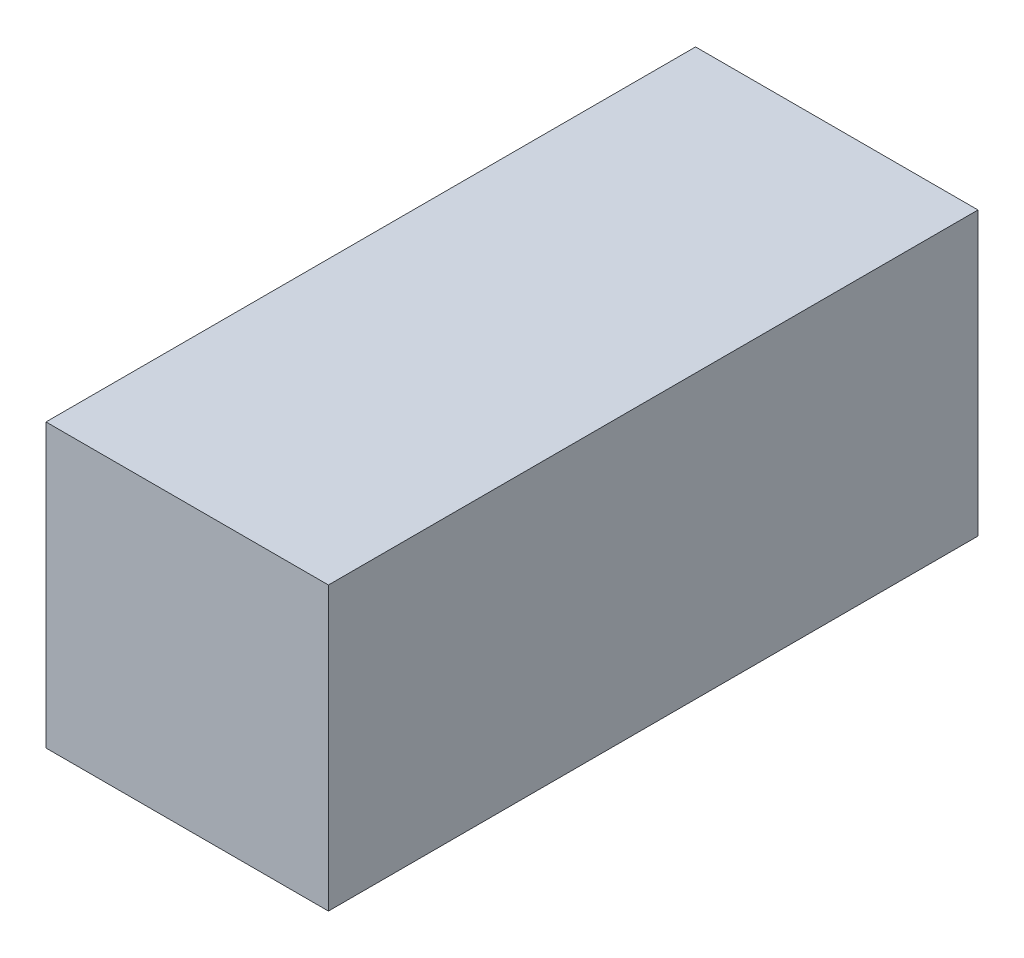
SolidWorks part; units mm, degrees
ref_plane "Front Plane" through (0, 0, 0) normal (0, 0, 1) x (1, 0, 0)
ref_plane "Top Plane" through (0, 0, 0) normal (0, 1, 0) x (1, 0, 0)
ref_plane "Right Plane" through (0, 0, 0) normal (1, 0, 0) x (0, 0, -1)
sketch "Sketch1" plane through (0, 0, 0) normal (0, 0, 1) x (1, 0, 0)
  line L1 (-50, -50) -> (50, -50)
  line L2 (-50, -50) -> (-50, 50)
  line L3 (-50, 50) -> (50, 50)
  line L4 (50, -50) -> (50, 50)
  line L5 (-50, -50) -> (50, 50) construction
  line L6 (-50, 50) -> (50, -50) construction
  point P0 (0, 0)
  dimension "D1" = 100
extrude "Boss-Extrude1" add sketch "Sketch1" along normal blind 230
ref_plane "Plane1" through (0, 0, 0) normal (-0.7071, 0.7071, 0) x (0.7071, 0.7071, 0)
ref_plane "Plane2" through (0, 0, 0) normal (-0.7071, -0.7071, 0) x (-0.7071, 0.7071, 0)
ref_axis "Axis1" through (0, 0, -11.5) along (0, 0, 1)
shell "Shell2" thickness 2.5
sketch "Sketch2" plane through (-47.5, 0, 0) normal (1, 0, 0) x (0, 0, -1)
  line L0 (-227.5, -47.5) -> (-2.5, -47.5) construction
  line L1 (-122.5, -47.5) -> (-22.5, -47.5)
  line L2 (-122.5, -47.5) -> (-122.5, 43.3365)
  line L3 (-122.5, 43.3365) -> (-22.5, 43.3365)
  line L4 (-22.5, -47.5) -> (-22.5, 43.3365)
  line L5 (-227.5, 47.5) -> (-2.5, 47.5) construction
  line L6 (-227.5, 47.5) -> (-2.5, 47.5)
  line L8 (-2.5, 47.5) -> (-2.5, -47.5) construction
  circle A0 centre (-12.5, -27.5) radius 10
  line M5 (-2.5, -47.5) -> (-2.5, 47.5)
  line M8 (-227.5, -47.5) -> (-2.5, -47.5)
  dimension "D4" = 20
  dimension "D1" = 100
  dimension "D2" = 20
  dimension "D3" = 20
extrude "Boss-Extrude2" add sketch "Sketch2" along normal blind 47.5 separate body contours L3 L2 M8 M5 region at (-47.5, -2.0817, 72.5)
extrude "Boss-Extrude3" add sketch "Sketch2<3>" along normal offset from surface (95 mm away) 2.5 separate body contours A0 region at (-47.5, -27.5, 12.5) up to face at (50, 0, 115)
sketch "Sketch2<3>" plane through (-47.5, 0, 0) normal (1, 0, 0) x (0, 0, -1) same geometry as "Sketch2"
sketch "Sketch4" plane through (0, 0, 2.5) normal (0, 0, 1) x (1, 0, 0)
  line L0 (47.5, 47.5) -> (-47.5, 47.5) construction
  line L1 (0, -47.5) -> (0, 43.3365) construction
  circle A0 centre (10, 27.5) radius 10
  dimension "D1" = 20
  dimension "D2" = 20
extrude "Boss-Extrude5" add sketch "Sketch4" along normal blind 100 separate body
sketch "Sketch5" plane through (0, 47.5, 0) normal (0, -1, 0) x (1, 0, 0)
  line L0 (47.5, 227.5) -> (47.5, 2.5) construction
  line L1 (0, 122.5) -> (-47.5, 122.5) construction
  line L3 (47.5, 87.5) -> (22.5, 87.5)
  line L4 (47.5, 87.5) -> (47.5, 27.5)
  line L5 (47.5, 27.5) -> (22.5, 27.5)
  line L6 (22.5, 87.5) -> (22.5, 27.5)
  circle A0 centre (37.5, 102.5) radius 10
  dimension "D1" = 20
  dimension "D2" = 20
  dimension "D3" = 25
  dimension "D4" = 60
  dimension "D5" = 15
extrude "Boss-Extrude7" add sketch "Sketch5" along normal up to next separate body
sketch "Sketch6" plane through (0, 0, 227.5) normal (0, 0, -1) x (-1, 0, 0)
  line L0 (-47.5, -47.5) -> (-47.5, 47.5) construction
  line L1 (45, 45) -> (-45, 45)
  line L2 (45, 45) -> (45, -45)
  line L3 (45, -45) -> (-45, -45)
  line L4 (-45, 45) -> (-45, -45)
  line L5 (45, 45) -> (-45, -45) construction
  line L6 (45, -45) -> (-45, 45) construction
  point P0 (0, 0)
  point P5 (-47.5, -47.5)
  point P6 (-44.2238, -44.5651)
  dimension "D1" = 2.5
extrude "Boss-Extrude8" add sketch "Sketch6" along normal blind 100
